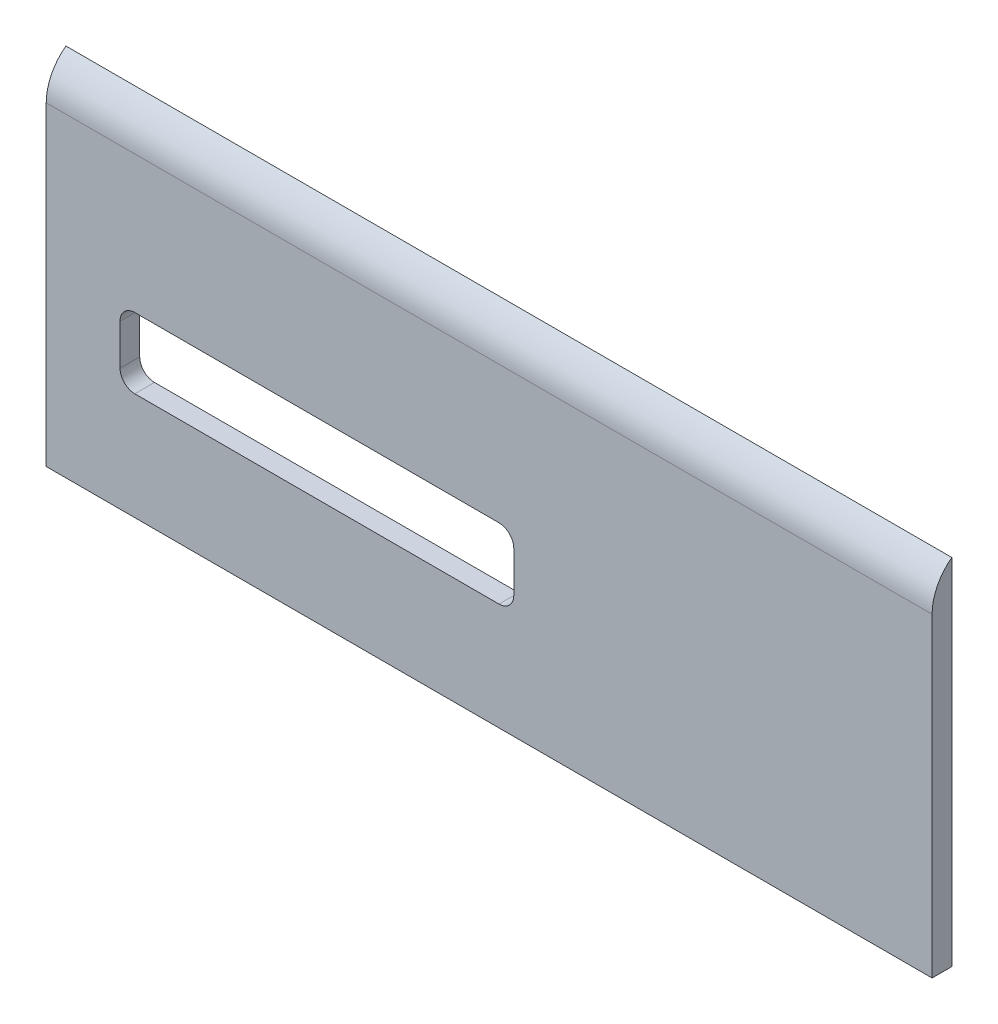
SolidWorks part; units mm, degrees
ref_plane "Alzado" through (0, 0, 0) normal (0, 0, 1) x (1, 0, 0)
ref_plane "Planta" through (0, 0, 0) normal (0, 1, 0) x (1, 0, 0)
ref_plane "Vista lateral" through (0, 0, 0) normal (1, 0, 0) x (0, 0, -1)
sketch "Croquis1" plane through (0, 0, 0) normal (0, 0, 1) x (1, 0, 0)
  line L1 (-98, 60) -> (-98, -4)
  line L2 (90, 60) -> (90, -4)
  line L3 (86, 68) -> (-94, 68) construction
  line L5 (86, -4) -> (-94, -4) construction
  line L9 (86, 68) -> (-94, 68)
  line L11 (90, -4) -> (-98, -4)
  arc A4 (90, 60) -> (86, 68) centre (80, 60) ccw construction
  arc A5 (90, 60) -> (86, 68) centre (80, 60) ccw
  arc A6 (-94, 68) -> (-98, 60) centre (-88, 60) ccw construction
  arc A7 (-94, 68) -> (-98, 60) centre (-88, 60) ccw
extrude "Saliente-Extruir1" add sketch "Croquis1" along normal blind 4
sketch "Croquis2" plane through (0, 0, 0) normal (0, 0, -1) x (-1, 0, 0)
  line L0 (4, 0) -> (4, 68) construction
  line L1 (-86, 0) -> (94, 0) construction
  line L2 (-86, 68) -> (94, 68) construction
  line L3 (-82, 0) -> (4, 0) construction
  line L4 (-39, 0) -> (-38.7, 71) construction
  line L5 (41.9915, 0) -> (41.9915, 4)
  line L6 (-33.9915, 0) -> (-43.9915, 0)
  line L7 (-33.9915, 0) -> (-33.9915, 4)
  line L8 (-33.9915, 4) -> (-43.9915, 4)
  line L9 (-43.9915, 0) -> (-43.9915, 4)
  line L10 (-33.9915, 0) -> (-43.9915, 4) construction
  line L11 (-33.9915, 4) -> (-43.9915, 0) construction
  line L12 (41.9915, 0) -> (51.9915, 0)
  line L13 (51.9915, 0) -> (51.9915, 4)
  line L14 (41.9915, 4) -> (51.9915, 4)
  point P15 (-38.9915, 2)
  dimension "D1" = 4
  dimension "D2" = 10
extrude "Saliente-Extruir2" add sketch "Croquis2" along normal blind 10
sketch "Croquis3" plane through (0, 0, 0) normal (0, -1, 0) x (1, 0, 0)
  line L1 (-41.9915, 0) -> (-51.9915, 0)
  line L2 (-41.9915, 0) -> (-41.9915, -10)
  line L3 (-41.9915, -10) -> (-51.9915, -10)
  line L4 (-51.9915, 0) -> (-51.9915, -10)
  line L5 (-41.9915, 0) -> (-51.9915, -10) construction
  line L6 (-41.9915, -10) -> (-51.9915, 0) construction
  line L7 (-44.2415, -3.4123) -> (-46.9915, -1.8246)
  line L8 (-46.9915, -1.8246) -> (-49.7415, -3.4123)
  line L9 (-49.7415, -3.4123) -> (-49.7415, -6.5877)
  line L10 (-49.7415, -6.5877) -> (-46.9915, -8.1754)
  line L11 (-46.9915, -8.1754) -> (-44.2415, -6.5877)
  line L12 (-44.2415, -6.5877) -> (-44.2415, -3.4123)
  line L13 (43.9915, 0) -> (33.9915, 0)
  line L14 (43.9915, 0) -> (43.9915, -10)
  line L15 (43.9915, -10) -> (33.9915, -10)
  line L16 (33.9915, 0) -> (33.9915, -10)
  line L17 (43.9915, 0) -> (33.9915, -10) construction
  line L18 (43.9915, -10) -> (33.9915, 0) construction
  line L19 (41.7415, -3.4123) -> (38.9915, -1.8246)
  line L20 (38.9915, -1.8246) -> (36.2415, -3.4123)
  line L21 (36.2415, -3.4123) -> (36.2415, -6.5877)
  line L22 (36.2415, -6.5877) -> (38.9915, -8.1754)
  line L23 (38.9915, -8.1754) -> (41.7415, -6.5877)
  line L24 (41.7415, -6.5877) -> (41.7415, -3.4123)
  circle A0 centre (-46.9915, -5) radius 1.5
  circle A1 centre (-46.9915, -5) radius 2.75 construction
  circle A2 centre (38.9915, -5) radius 1.5
  circle A3 centre (38.9915, -5) radius 2.75 construction
  point P4 (-46.9915, -5)
  point P20 (38.9915, -5)
  dimension "D1" = 5.5
  dimension "D2" = 3
  dimension "D4" = 3
  dimension "D3" = 5.5
extrude "Cortar-Extruir1" cut sketch "Croquis3" against normal blind 10 contours A2 | A0 region at (-46.9915, 0, -5) region at (38.9915, 0, -5)
extrude "Cortar-Extruir2" cut sketch "Croquis3<3>" against normal blind 1.65 contours L11 L12 L7 L8 L9 L10 A0 | L23 L24 L19 L20 L21 L22 A2 region at (-44.3256, 0, -5) region at (41.6575, 0, -5)
sketch "Croquis3<3>" plane through (0, 0, 0) normal (0, -1, 0) x (1, 0, 0) same geometry as "Croquis3"
fillet "Redondeo2" radius 10 1 edges at (-4, 68, 4)
sketch "Croquis4" plane through (0, 0, 4) normal (0, 0, 1) x (1, 0, 0)
  line L1 (86, 68) -> (90, 68)
  line L2 (86, 68) -> (86, -4)
  line L3 (86, -4) -> (90, -4)
  line L4 (90, 68) -> (90, -4)
  line L5 (86, 68) -> (90, -4) construction
  line L6 (86, -4) -> (90, 68) construction
  line L7 (-94, 68) -> (-98, 68)
  line L8 (-94, 68) -> (-94, -4)
  line L9 (-94, -4) -> (-98, -4)
  line L10 (-98, 68) -> (-98, -4)
  line L11 (-94, 68) -> (-98, -4) construction
  line L12 (-94, -4) -> (-98, 68) construction
  point P4 (88, 32)
  point P11 (-96, 32)
extrude "Cortar-Extruir3" cut sketch "Croquis4" against normal up to surface (4 mm away) up to face at (38.9915, 2, 0)
sketch "Croquis5" plane through (0, 0, 4) normal (0, 0, 1) x (1, 0, 0)
  line L0 (-94, -4) -> (86, -4) construction
  line L1 (-79, 17.8) -> (1, 17.8)
  line L2 (-79, 17.8) -> (-79, 32.1)
  line L3 (-79, 32.1) -> (1, 32.1)
  line L4 (1, 17.8) -> (1, 32.1)
  line L5 (-79, 17.8) -> (1, 32.1) construction
  line L6 (-79, 32.1) -> (1, 17.8) construction
  line L7 (-94, -4) -> (-94, 60) construction
  point P4 (-39, 24.95)
  dimension "D1" = 14.3
  dimension "D2" = 21.8
  dimension "D3" = 15
  dimension "D4" = 80
extrude "Cortar-Extruir4" cut sketch "Croquis5" against normal up to next
fillet "Redondeo3" radius 3 4 edges at (1, 32.1, 2) (1, 17.8, 2) (-79, 32.1, 2) (-79, 17.8, 2)
